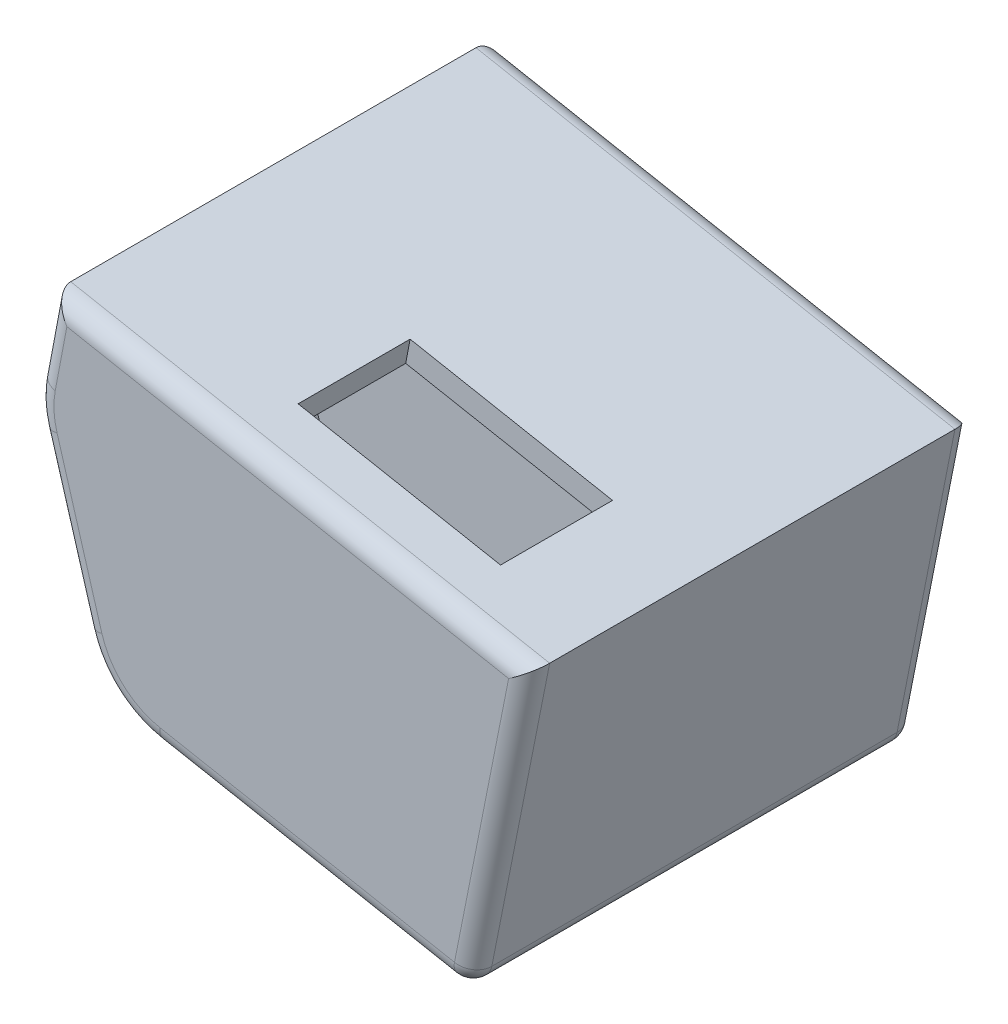
SolidWorks part; units mm, degrees
ref_plane "前视基准面" through (0, 0, 0) normal (0, 0, 1) x (1, 0, 0)
ref_plane "上视基准面" through (0, 0, 0) normal (0, 1, 0) x (1, 0, 0)
ref_plane "右视基准面" through (0, 0, 0) normal (1, 0, 0) x (0, 0, -1)
sketch "草图7" plane through (0, 0, 0) normal (0, 0, 1) x (1, 0, 0)
  line L0 (51.6183, 4.889) -> (54.8861, 4.2684)
  line L1 (54.8861, 4.2684) -> (61.4108, 37.1377)
  line L2 (60.4284, 37.3243) -> (62.3933, 36.9511) construction
  line L3 (61.4108, 37.1377) -> (10.5918, 46.7894)
  line L4 (19.7873, 10.9345) -> (15.7117, 11.7085)
  line L5 (15.7117, 11.7085) -> (8.5308, 35.9377)
  line L6 (8.5308, 35.9377) -> (10.5918, 46.7894)
  line L7 (-227.426, 91.9946) -> (60.4284, 37.3243) construction
extrude "拉伸-薄壁3" add sketch "草图7" along normal mid plane 42 thin thin type one direction wall 2.5
sketch "草图8" plane through (0, 0, 21) normal (0, 0, 1) x (1, 0, 0)
  line L0 (19.7873, 10.9345) -> (51.6183, 4.889)
  line L14 (52.9167, 7.1871) -> (52.0848, 7.3451)
  line L15 (52.0848, 7.3451) -> (51.6183, 4.889)
  line L16 (51.6183, 4.889) -> (54.8861, 4.2684)
  line L17 (54.8861, 4.2684) -> (61.4108, 37.1377)
  line L18 (61.4108, 37.1377) -> (10.5918, 46.7894)
  line L19 (10.5918, 46.7894) -> (8.5308, 35.9377)
  line L20 (8.5308, 35.9377) -> (15.7117, 11.7085)
  line L21 (15.7117, 11.7085) -> (19.7873, 10.9345)
  line L22 (19.7873, 10.9345) -> (20.2538, 13.3906)
  line L23 (20.2538, 13.3906) -> (17.6755, 13.8802)
  line L24 (17.6755, 13.8802) -> (11.1, 36.0668)
  line L25 (11.1, 36.0668) -> (12.5814, 43.8669)
  line L26 (12.5814, 43.8669) -> (58.4679, 35.152)
  line L27 (58.4679, 35.152) -> (52.9167, 7.1871)
  line L30 (51.6183, 4.889) -> (54.8861, 4.2684)
  line L31 (54.8861, 4.2684) -> (61.4108, 37.1377)
  line L32 (61.4108, 37.1377) -> (10.5918, 46.7894)
  line L33 (10.5918, 46.7894) -> (8.5308, 35.9377)
  line L34 (8.5308, 35.9377) -> (15.7117, 11.7085)
  line L35 (15.7117, 11.7085) -> (19.7873, 10.9345)
  line L36 (19.7873, 10.9345) -> (20.2538, 13.3906)
  line M15 (52.9167, 7.1871) -> (52.0848, 7.3451)
  line M16 (52.0848, 7.3451) -> (51.6183, 4.889)
  line M17 (51.6183, 4.889) -> (54.8861, 4.2684)
  line M18 (54.8861, 4.2684) -> (61.4108, 37.1377)
  line M19 (61.4108, 37.1377) -> (10.5918, 46.7894)
  line M20 (10.5918, 46.7894) -> (8.5308, 35.9377)
  line M21 (8.5308, 35.9377) -> (15.7117, 11.7085)
  line M22 (15.7117, 11.7085) -> (19.7873, 10.9345)
  line M23 (19.7873, 10.9345) -> (20.2538, 13.3906)
  line M24 (20.2538, 13.3906) -> (17.6755, 13.8802)
  line M25 (17.6755, 13.8802) -> (11.1, 36.0668)
  line M26 (11.1, 36.0668) -> (12.5814, 43.8669)
  line M27 (12.5814, 43.8669) -> (58.4679, 35.152)
  line M28 (58.4679, 35.152) -> (52.9167, 7.1871)
  dimension "D1" = 0
extrude "凸台-拉伸1" add sketch "草图8" along normal blind 2.5 contours M28 M15 M16 M17 M18 M19 M20 M21 M22 M23 M24 M25 M26 M27 | L0 M23 M16 M15 M28 M27 M26 M25 M24
sketch "草图9" plane through (0, 0, -3.5) normal (0, 0, 1) x (1, 0, 0)
  line L0 (24.3972, 10.0589) -> (26.7109, 22.2412)
  line L1 (19.7873, 10.9345) -> (51.6183, 4.889) construction
  line L2 (22.101, 23.1167) -> (26.915, 22.2024) construction
  line L3 (26.7109, 22.2412) -> (49.4054, 17.931)
  line L4 (49.1181, 17.9855) -> (53.932, 17.0713) construction
  line L5 (49.4054, 17.931) -> (47.0917, 5.7487)
  line L6 (47.0917, 5.7487) -> (54.8861, 4.2684)
  line L7 (54.8861, 4.2684) -> (61.4108, 37.1377)
  line L8 (61.4108, 37.1377) -> (10.5918, 46.7894)
  line L9 (10.5918, 46.7894) -> (8.5308, 35.9377)
  line L10 (8.5308, 35.9377) -> (15.7117, 11.7085)
  line L11 (15.7117, 11.7085) -> (24.3972, 10.0589)
  circle A0 centre (23.4003, 16.5591) radius 1.25
  circle A1 centre (50.3191, 11.4466) radius 1.25
extrude "凸台-拉伸2" add sketch "草图9" along normal blind 2.5
sketch "草图10" plane through (0, 0, -21) normal (0, 0, -1) x (-1, 0, 0)
  line L5 (-15.7117, 11.7085) -> (-8.5308, 35.9377)
  line L6 (-54.8861, 4.2684) -> (-15.7117, 11.7085)
  line L7 (-61.4108, 37.1377) -> (-54.8861, 4.2684)
  line L8 (-10.5918, 46.7894) -> (-61.4108, 37.1377)
  line L9 (-8.5308, 35.9377) -> (-10.5918, 46.7894)
  line L10 (-15.7117, 11.7085) -> (-8.5308, 35.9377)
  line L11 (-54.8861, 4.2684) -> (-15.7117, 11.7085)
  line L12 (-61.4108, 37.1377) -> (-54.8861, 4.2684)
  line L13 (-10.5918, 46.7894) -> (-61.4108, 37.1377)
  line L14 (-8.5308, 35.9377) -> (-10.5918, 46.7894)
  dimension "D1" = 0
extrude "凸台-拉伸3" add sketch "草图10" along normal blind 2.5
sketch "草图11" plane through (17.633, 5.226, 0) normal (-0.9588, -0.2842, 0) x (0, 0, 1)
  line L0 (21, 4.861) -> (21, -9.9803) construction
  line L1 (21, 2.3916) -> (-21, 2.3916)
  line L2 (21, 2.3916) -> (21, 12.7979)
  line L3 (21, 12.7979) -> (-21, 12.7979)
  line L4 (-21, 2.3916) -> (-21, 12.7979)
extrude "切除-拉伸1" cut sketch "草图11" against normal blind 5
fillet "圆角1" radius 10 10 edges at (22.8175, 10.359, -3.5) (22.8175, 10.359, -1) (15.7117, 11.7085, -22.25) (21.2377, 10.659, -2.25) (14.854, 14.6024, 21) (13.9963, 17.4963, 0) (14.854, 14.6024, -21) (15.7117, 11.7085, 22.25) (8.5308, 35.9377, 0)
fillet "圆角2" radius 2 15 edges at (36.0013, 41.9636, -23.5) (58.1484, 20.7031, -23.5) (38.2936, 7.4197, -23.5) (11.5996, 25.5832, 23.5) (11.5996, 25.5832, -23.5) (9.7875, 42.5548, -23.5) (16.8599, 12.9783, -23.5) (8.8202, 35.9523, -23.5) (38.2936, 7.4197, 23.5) (16.8599, 12.9783, 23.5) (8.8202, 35.9523, 23.5) (54.8861, 4.2684, 0) (58.1484, 20.7031, 23.5) (36.0013, 41.9636, 23.5) (9.7875, 42.5548, 23.5)
sketch "草图12" plane through (8.4793, 44.646, 0) normal (-0.1866, -0.9824, 0) x (0.9824, -0.1866, 0)
  line L1 (43.4556, 16.9403) -> (21.5963, 16.9403)
  line L2 (43.4556, 16.9403) -> (43.4556, 5.0602)
  line L3 (43.4556, 5.0602) -> (21.5963, 5.0602)
  line L4 (21.5963, 16.9403) -> (21.5963, 5.0602)
extrude "切除-拉伸2" cut sketch "草图12" against normal blind 61
sketch "草图14" plane through (0, 0, -23.5) normal (0, 0, -1) x (-1, 0, 0)
  circle A0 centre (-50.3191, 11.4466) radius 2
  circle A1 centre (-23.4003, 16.5591) radius 2
extrude "切除-拉伸3" cut sketch "草图14" against normal blind 10
